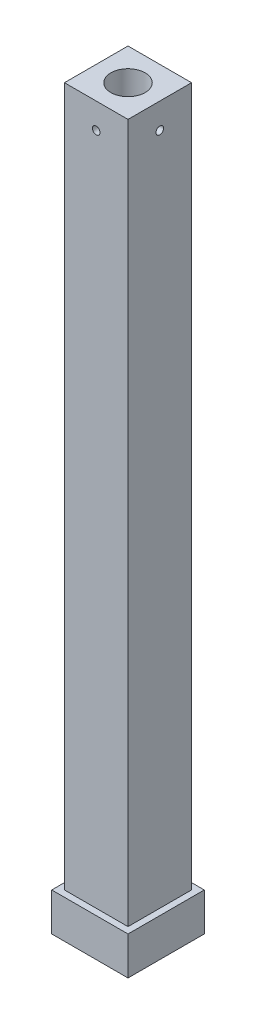
SolidWorks part; units mm, degrees
ref_plane "前视基准面" through (0, 0, 0) normal (0, 0, 1) x (1, 0, 0)
ref_plane "上视基准面" through (0, 0, 0) normal (0, 1, 0) x (1, 0, 0)
ref_plane "右视基准面" through (0, 0, 0) normal (1, 0, 0) x (0, 0, -1)
other "Configuration Table"
sketch "草图1" plane through (0, 0, 0) normal (0, 1, 0) x (1, 0, 0)
  line L1 (2.8868, 0) -> (1.4434, 2.5)
  line L2 (1.4434, 2.5) -> (-1.4434, 2.5)
  line L3 (-1.4434, 2.5) -> (-2.8868, 0)
  line L4 (-2.8868, 0) -> (-1.4434, -2.5)
  line L5 (-1.4434, -2.5) -> (1.4434, -2.5)
  line L6 (1.4434, -2.5) -> (2.8868, 0)
  line L7 (-2.5, -2.5) -> (2.5, -2.5)
  line L8 (-2.5, -2.5) -> (-2.5, 2.5)
  line L9 (-2.5, 2.5) -> (2.5, 2.5)
  line L10 (2.5, -2.5) -> (2.5, 2.5)
  line L11 (-2.5, -2.5) -> (2.5, 2.5) construction
  line L12 (-2.5, 2.5) -> (2.5, -2.5) construction
  line L13 (-3, -3) -> (3, -3)
  line L14 (-3, -3) -> (-3, 3)
  line L15 (-3, 3) -> (3, 3)
  line L16 (3, -3) -> (3, 3)
  line L17 (-3, -3) -> (3, 3) construction
  line L18 (-3, 3) -> (3, -3) construction
  circle A0 centre (0, 0) radius 2.5 construction
  circle A1 centre (0, 0) radius 1.35
  dimension "D1" = 5
  dimension "D3" = 2.7
  dimension "D2" = 5
  dimension "D4" = 6
extrude "凸台-拉伸1" add sketch "草图1" along normal blind 58 contours L9 L10 L7 L8
extrude "凸台-拉伸2" add sketch "草图1<5>" along normal blind 3 contours L15 L16 L13 L14
sketch "草图1<5>" plane through (0, 0, 0) normal (0, 1, 0) x (1, 0, 0) same geometry as "草图1"
extrude "切除-拉伸1" cut sketch "草图1<3>" along normal through all contours A1 region at (0, 0, 0)
sketch "草图1<3>" plane through (0, 0, 0) normal (0, 1, 0) x (1, 0, 0) same geometry as "草图1"
extrude "切除-拉伸2" cut sketch "草图1<4>" along normal blind 2 contours L1 L2 L3 L4 L5 L6
sketch "草图1<4>" plane through (0, 0, 0) normal (0, 1, 0) x (1, 0, 0) same geometry as "草图1"
sketch "草图3" plane through (0, 0, 2.5) normal (0, 0, 1) x (1, 0, 0)
  line L0 (-2.5, 58) -> (2.5, 58) construction
  line L1 (-2.5, 56) -> (2.5, 56) construction
  line L2 (-2.5, 58) -> (-2.5, 3) construction
  line L3 (2.5, 58) -> (2.5, 3) construction
  circle A0 centre (0, 56) radius 0.3
  dimension "D1" = 0.6
  dimension "D2" = 2
extrude "切除-拉伸3" cut sketch "草图3" against normal through all
sketch "草图4" plane through (-2.5, 0, 0) normal (-1, 0, 0) x (0, 0, 1)
  line L0 (-2.5, 56) -> (2.5, 56) construction
  line L1 (-2.5, 58) -> (-2.5, 3) construction
  line L2 (2.5, 58) -> (2.5, 3) construction
  line L3 (2.5, 58) -> (-2.5, 58) construction
  circle A0 centre (0, 56) radius 0.3
  dimension "D1" = 0.6
  dimension "D2" = 2
extrude "切除-拉伸4" cut sketch "草图4" against normal through all
